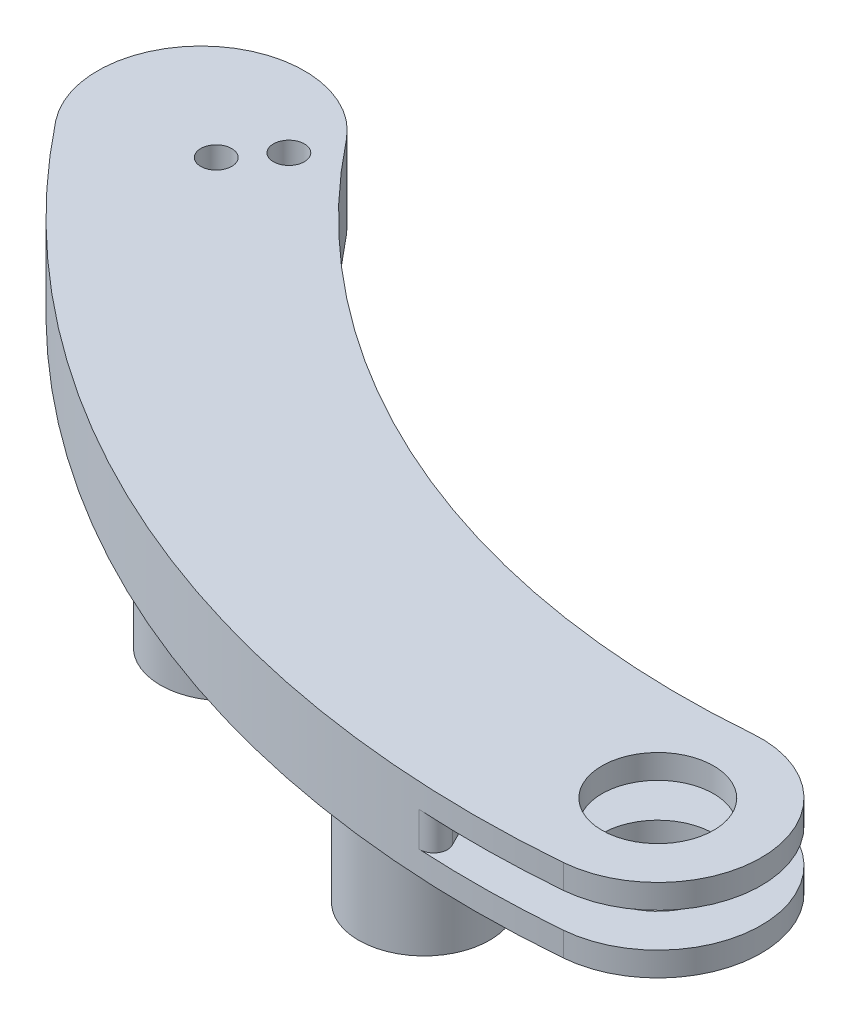
SolidWorks part; units mm, degrees
ref_plane "Front Plane" through (0, 0, 0) normal (0, 0, 1) x (1, 0, 0)
ref_plane "Top Plane" through (0, 0, 0) normal (0, 1, 0) x (1, 0, 0)
ref_plane "Right Plane" through (0, 0, 0) normal (1, 0, 0) x (0, 0, -1)
sketch "Sketch1" plane through (0, 0, 0) normal (0, 1, 0) x (1, 0, 0)
  arc A0 (0, 0) -> (-117, 50.7404) centre (-11.1561, 134.5383) cw construction
  arc A1 (-128.7604, 41.4296) -> (1.2396, -14.9487) centre (-11.1561, 134.5383) ccw
  arc A2 (-105.2396, 60.0513) -> (-1.2396, 14.9487) centre (-11.1561, 134.5383) ccw
  arc A3 (-105.2396, 60.0513) -> (-128.7604, 41.4296) centre (-117, 50.7404) ccw
  arc A4 (1.2396, -14.9487) -> (-1.2396, 14.9487) centre (0, 0) ccw
  arc A5 (-16.6792, 14.6654) -> (-15.4249, -15.401) centre (4.9458, 0.5082) ccw
  point P3 (-64.8692, 10.6839)
  dimension "D3" = 30
  dimension "D4" = 150
  dimension "D1" = 75
  dimension "D2" = 130
extrude "Boss-Extrude4" add sketch "Sketch1" along normal blind 12 contours A5 A2 A3 A1 region at (-76.6272, 0, -21.3687)
extrude "Boss-Extrude5" add sketch "Sketch1<6>" along normal blind 3.5 contours A2 A5 A1 A4 region at (-3.6374, 0, 0.1249)
sketch "Sketch1<6>" plane through (0, 0, 0) normal (0, 1, 0) x (1, 0, 0) same geometry as "Sketch1"
extrude "Boss-Extrude6" add sketch "Sketch1<8>" along normal blind 12 contours A2 A5 A1 A4 region at (-3.6374, 0, 0.1249)
sketch "Sketch1<8>" plane through (0, 0, 0) normal (0, 1, 0) x (1, 0, 0) same geometry as "Sketch1"
extrude "Cut-Extrude2" cut sketch "Sketch1<9>" along normal blind 8.5 contours A2 A5 A1 A4 region at (-3.6374, 0, 0.1249)
sketch "Sketch1<9>" plane through (0, 0, 0) normal (0, 1, 0) x (1, 0, 0) same geometry as "Sketch1"
extrude "Boss-Extrude7" add sketch "Sketch1<10>" along normal blind 3.5 contours A2 A5 A1 A4 region at (-3.6374, 0, 0.1249)
sketch "Sketch1<10>" plane through (0, 0, 0) normal (0, 1, 0) x (1, 0, 0) same geometry as "Sketch1"
sketch "Sketch2" plane through (0, 12, 0) normal (0, 1, 0) x (1, 0, 0)
  circle A0 centre (0, 0) radius 8.1
  dimension "D1" = 16.2
extrude "Cut-Extrude3" cut sketch "Sketch2" against normal blind 12
fillet "Fillet1" radius 5 1 edges at (-16.6792, 6, -14.6654)
fillet "Fillet2" radius 2 1 edges at (-15.4249, 6, 15.401)
sketch "Sketch3" plane through (0, 12, 0) normal (0, 1, 0) x (1, 0, 0)
  circle A0 centre (-107.8166, 54.3025) radius 2.25
  circle A1 centre (-112.4991, 48.4438) radius 2.25
  dimension "D1" = 4.5
  dimension "D2" = 4.5
  dimension "D3" = 7.5
  dimension "D4" = 6.3
extrude "Cut-Extrude4" cut sketch "Sketch3" against normal blind 12
sketch "Sketch4" plane through (0, 0, 0) normal (0, 1, 0) x (1, 0, 0)
  circle A0 centre (-35.8241, 1.9278) radius 8
  circle A1 centre (-35.8241, 1.9278) radius 9.5
  circle A2 centre (-82.2472, 19.6043) radius 8
  circle A3 centre (-82.2472, 19.6043) radius 9.5
  dimension "D1" = 16
  dimension "D2" = 19
extrude "Boss-Extrude8" add sketch "Sketch4" against normal blind 20
